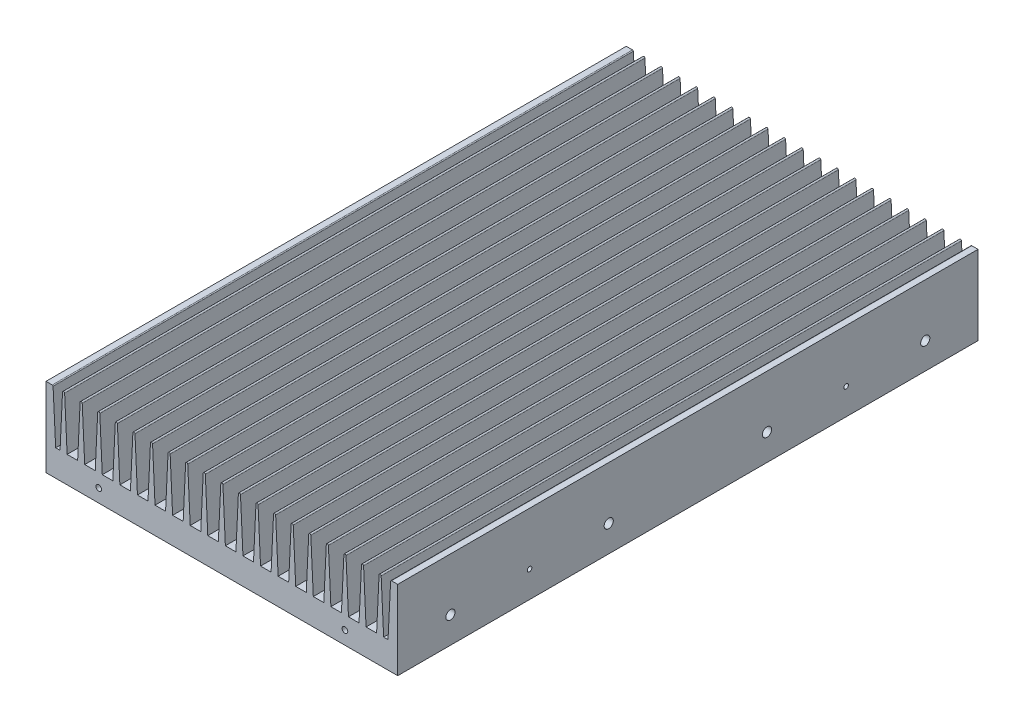
SolidWorks part; units mm, degrees
ref_plane "Спереди" through (0, 0, 0) normal (0, 0, 1) x (1, 0, 0)
ref_plane "Сверху" through (0, 0, 0) normal (0, 1, 0) x (1, 0, 0)
ref_plane "Справа" through (0, 0, 0) normal (1, 0, 0) x (0, 0, -1)
sketch "Эскиз1" plane through (0, 0, 0) normal (0, 0, 1) x (1, 0, 0)
  line L0 (0, 45) -> (3.5244, 45)
  line L1 (0, 0) -> (200, 0)
  line L2 (4.0238, 44.525) -> (5.5, 15)
  line L3 (0, 45) -> (0, 0)
  line L4 (200, 45) -> (200, 0)
  line L5 (100, 63.7127) -> (100, -22.2582) construction
  line L8 (200, 45) -> (196.4756, 45)
  line L9 (195.9762, 44.525) -> (194.5, 15)
  line L10 (5.5, 15) -> (194.5, 15)
  arc A0 (3.5244, 45) -> (4.0238, 44.525) centre (3.5244, 44.5) cw
  arc A2 (196.4756, 45) -> (195.9762, 44.525) centre (196.4756, 44.5) ccw
  point P18 (196, 45)
  dimension "D9" = 0.5
  dimension "D1" = 200
  dimension "D2" = 15
  dimension "D3" = 5.5
  dimension "D4" = 45
  dimension "D7" = 4
extrude "Вытянуть1" add sketch "Эскиз1" along normal blind 330
sketch "Эскиз2" plane through (0, 0, 330) normal (0, 0, 1) x (1, 0, 0)
  line L0 (194.5, 15) -> (5.5, 15) construction
  line L1 (9.4007, 44.4285) -> (8, 15)
  line L2 (10, 45) -> (10, 22.5548) construction
  line L3 (10.5993, 44.4285) -> (12, 15)
  line L4 (8, 15) -> (12, 15)
  line L6 (0, 45) -> (0, 0) construction
  arc A0 (9.4007, 44.4285) -> (10.5993, 44.4285) centre (10, 44.4) cw
  dimension "D1" = 30
  dimension "D3" = 0.6
  dimension "D2" = 4
  dimension "D4" = 10
extrude "Вытянуть3" add sketch "Эскиз2" against normal blind 330
pattern_curve "Кривая1" of "Вытянуть3" along edge at (100, 0, 0) parameters "D1"=19, "D3"=10, "D2"=1, "D4"=50
sketch "Эскиз3" plane through (0, 0, 0) normal (0, -1, 0) x (1, 0, 0)
  line L0 (0, 330) -> (0, 0) construction
  line L1 (0, 0) -> (200, 0) construction
  line L2 (200, 330) -> (200, 0) construction
  circle A0 centre (9.5, 19.5) radius 2.1
  circle A1 centre (188.5, 40) radius 2.1
  circle A2 centre (163.5, 130) radius 2.1
  circle A3 centre (11.5, 151) radius 2.1
  circle A4 centre (63.5, 189) radius 2.1
  circle A5 centre (16.5, 240) radius 2.1
  circle A6 centre (39.5, 79.5) radius 2.6
  circle A7 centre (114.5, 30) radius 2.1
  circle A8 centre (181.5, 210) radius 2.1
  circle A9 centre (16.58, 183.75) radius 2.6
  circle A10 centre (84, 49) radius 1.3
  circle A11 centre (89, 89) radius 1.3
  circle A12 centre (61.5, 170) radius 1.3
  circle A13 centre (61.5, 210) radius 1.3
  circle A14 centre (108.5, 190) radius 1.3
  circle A15 centre (138, 189.5) radius 2.1
  dimension "D1" = 4.2
  dimension "D3" = 19.5
  dimension "D12" = 240
  dimension "D15" = 18.5
  dimension "D16" = 4.2
  dimension "D21" = 5.2
  dimension "D23" = 183.75
  dimension "D24" = 5.2
  dimension "D25" = 2.6
  dimension "D27" = 89
  dimension "D31" = 61.5
  dimension "D32" = 108.5
  dimension "D33" = 210
  dimension "D34" = 170
  dimension "D35" = 190
  dimension "D36" = 138
  dimension "D37" = 189.5
  dimension "D38" = 4.2
  dimension "D2" = 9.5
  dimension "D4" = 188.5
  dimension "D5" = 40
  dimension "D6" = 130
  dimension "D7" = 36.5
  dimension "D8" = 151
  dimension "D9" = 11.5
  dimension "D10" = 189
  dimension "D11" = 63.5
  dimension "D13" = 16.5
  dimension "D14" = 210
  dimension "D17" = 30
  dimension "D18" = 114.5
  dimension "D19" = 79.5
  dimension "D20" = 39.5
  dimension "D22" = 16.58
  dimension "D26" = 89
  dimension "D28" = 49
  dimension "D29" = 84
  dimension "D30" = 61.5
extrude "Вырез-Вытянуть1" cut sketch "Эскиз3" against normal blind 8
cosmetic thread "Условное изображение резьбы19" parameters "D2"=3
cosmetic thread "Условное изображение резьбы20" parameters "D2"=3
cosmetic thread "Условное изображение резьбы21" parameters "D2"=3
cosmetic thread "Условное изображение резьбы22" parameters "D2"=3
cosmetic thread "Условное изображение резьбы23" parameters "D2"=3
cosmetic thread "Условное изображение резьбы36" parameters "D2"=6
cosmetic thread "Условное изображение резьбы37" parameters "D2"=5
cosmetic thread "Условное изображение резьбы38" parameters "D2"=5
cosmetic thread "Условное изображение резьбы39" parameters "D2"=5
cosmetic thread "Условное изображение резьбы40" parameters "D2"=5
cosmetic thread "Условное изображение резьбы41" parameters "D2"=5
cosmetic thread "Условное изображение резьбы42" parameters "D2"=5
cosmetic thread "Условное изображение резьбы43" parameters "D2"=5
cosmetic thread "Условное изображение резьбы44" parameters "D2"=5
cosmetic thread "Условное изображение резьбы45" parameters "D2"=5
cosmetic thread "Условное изображение резьбы46" parameters "D2"=5
cosmetic thread "Условное изображение резьбы47" parameters "D2"=5
cosmetic thread "Условное изображение резьбы48" parameters "D2"=5
cosmetic thread "Условное изображение резьбы49" parameters "D2"=5
cosmetic thread "Условное изображение резьбы50" parameters "D2"=5
cosmetic thread "Условное изображение резьбы51" parameters "D2"=5
cosmetic thread "Условное изображение резьбы52" parameters "D2"=5
cosmetic thread "Условное изображение резьбы53" parameters "D2"=5
cosmetic thread "Условное изображение резьбы54" parameters "D2"=5
sketch "Эскиз4" plane through (0, 0, 0) normal (-1, 0, 0) x (0, 0, 1)
  line L0 (-12.5868, 15) -> (319.6217, 15) construction
  line L2 (330, 0) -> (0, 0) construction
  line L3 (165, 111.6371) -> (165, -16.336) construction
  line L4 (0, 44.4285) -> (0, 15) construction
  line L5 (330, 45) -> (330, 0) construction
  line L6 (0, 45) -> (0, 0) construction
  circle A0 centre (30, 15) radius 2.6
  circle A1 centre (75, 15) radius 1.3
  circle A2 centre (120, 15) radius 2.6
  circle A3 centre (210, 15) radius 2.6
  circle A4 centre (255, 15) radius 1.3
  circle A5 centre (300, 15) radius 2.6
  dimension "D3" = 45
  dimension "D4" = 45
  dimension "D5" = 5.2
  dimension "D6" = 2.6
  dimension "D1" = 15
  dimension "D2" = 30
extrude "Вырез-Вытянуть2" cut sketch "Эскиз4" against normal blind 8
cosmetic thread "Условное изображение резьбы1" parameters "D2"=6
cosmetic thread "Условное изображение резьбы2" parameters "D2"=6
cosmetic thread "Условное изображение резьбы3" parameters "D2"=6
cosmetic thread "Условное изображение резьбы4" parameters "D2"=6
cosmetic thread "Условное изображение резьбы9" parameters "D2"=6
cosmetic thread "Условное изображение резьбы10" parameters "D2"=6
cosmetic thread "Условное изображение резьбы17" parameters "D2"=3
cosmetic thread "Условное изображение резьбы18" parameters "D2"=3
sketch "Эскиз6" plane through (200, 0, 0) normal (1, 0, 0) x (0, 0, -1)
  circle A0 centre (-30, 15) radius 2.6 construction
  circle A1 centre (-30, 15) radius 2.6
  circle A2 centre (-75, 15) radius 1.3 construction
  circle A3 centre (-75, 15) radius 1.3
  circle A4 centre (-120, 15) radius 2.6 construction
  circle A5 centre (-120, 15) radius 2.6
  circle A6 centre (-210, 15) radius 2.6 construction
  circle A7 centre (-210, 15) radius 2.6
  circle A8 centre (-255, 15) radius 1.3 construction
  circle A9 centre (-255, 15) radius 1.3
  circle A10 centre (-300, 15) radius 2.6 construction
  circle A11 centre (-300, 15) radius 2.6
extrude "Вырез-Вытянуть5" cut sketch "Эскиз6" against normal blind 10
cosmetic thread "Условное изображение резьбы5" parameters "D2"=6
cosmetic thread "Условное изображение резьбы6" parameters "D2"=6
cosmetic thread "Условное изображение резьбы7" parameters "D2"=6
cosmetic thread "Условное изображение резьбы8" parameters "D2"=6
cosmetic thread "Условное изображение резьбы11" parameters "D2"=6
cosmetic thread "Условное изображение резьбы12" parameters "D2"=6
cosmetic thread "Условное изображение резьбы13" parameters "D2"=6
cosmetic thread "Условное изображение резьбы14" parameters "D2"=6
cosmetic thread "Условное изображение резьбы15" parameters "D2"=3
cosmetic thread "Условное изображение резьбы16" parameters "D2"=3
sketch "Эскиз7" plane through (0, 0, 330) normal (0, 0, 1) x (1, 0, 0)
  line L0 (-4.7281, 7.5) -> (192.2158, 7.5) construction
  line L1 (0, 0) -> (200, 0) construction
  line L2 (100, -30.4058) -> (100, 91.3521) construction
  line L3 (0, 45) -> (0, 0) construction
  line L4 (200, 0) -> (200, 45) construction
  circle A0 centre (30, 7.5) radius 1.6
  circle A1 centre (170, 7.5) radius 1.6
  dimension "D2" = 140
  dimension "D3" = 3.2
  dimension "D1" = 7.5
extrude "Вырез-Вытянуть6" cut sketch "Эскиз7" against normal blind 8
cosmetic thread "Условное изображение резьбы24" parameters "D2"=4
cosmetic thread "Условное изображение резьбы25" parameters "D2"=4
sketch "Эскиз8" plane through (0, 0, 0) normal (0, 0, -1) x (-1, 0, 0)
  circle A0 centre (-30, 7.5) radius 1.6 construction
  circle A1 centre (-30, 7.5) radius 1.6
  circle A2 centre (-170, 7.5) radius 1.6 construction
  circle A3 centre (-170, 7.5) radius 1.6
extrude "Вырез-Вытянуть7" cut sketch "Эскиз8" against normal blind 8
cosmetic thread "Условное изображение резьбы26" parameters "D2"=4
cosmetic thread "Условное изображение резьбы27" parameters "D2"=4
sketch "Эскиз9" plane through (0, 0, 0) normal (0, -1, 0) x (1, 0, 0)
  line L0 (0, 330) -> (200, 330) construction
  line L1 (200, 330) -> (200, 0) construction
  circle A0 centre (147, 320) radius 1.6
  circle A1 centre (147, 265) radius 1.6
  dimension "D1" = 55
  dimension "D2" = 10
  dimension "D3" = 3.2
  dimension "D4" = 53
  dimension "D5" = 53
extrude "Вырез-Вытянуть8" cut sketch "Эскиз9" against normal blind 8
cosmetic thread "Условное изображение резьбы55" parameters "D2"=4
cosmetic thread "Условное изображение резьбы56" parameters "D2"=4
sketch "Эскиз10" plane through (0, 0, 0) normal (0, -1, 0) x (1, 0, 0)
  line L0 (90.951, 292.5) -> (206.8991, 292.5) construction
  line L1 (147, 265) -> (147, 287.2235) construction
  circle A0 centre (147, 320) radius 1.6 construction
  circle A1 centre (147, 265) radius 1.6 construction
  circle A2 centre (111.4539, 292.5) radius 1.6
  circle A3 centre (182.5461, 292.5) radius 1.6
  dimension "D1" = 3.2
extrude "Вырез-Вытянуть9" cut sketch "Эскиз10" against normal blind 10
cosmetic thread "Условное изображение резьбы57"
cosmetic thread "Условное изображение резьбы58"
